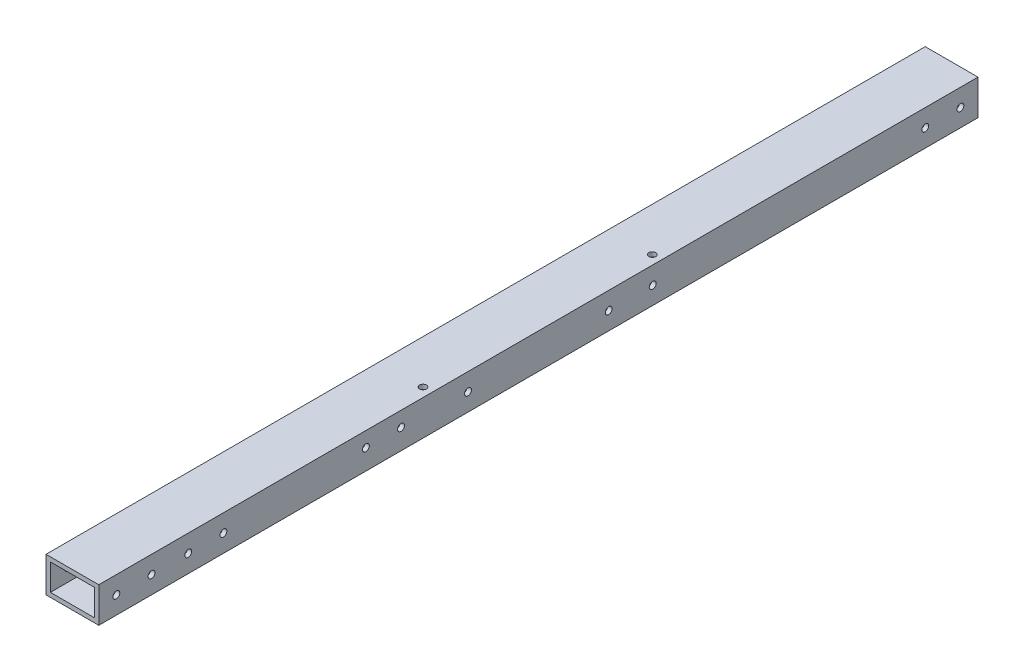
SolidWorks part; units mm, degrees
material "1060 Alloy"
ref_plane "Front Plane" through (0, 0, 0) normal (0, 0, 1) x (1, 0, 0)
ref_plane "Top Plane" through (0, 0, 0) normal (0, 1, 0) x (1, 0, 0)
ref_plane "Right Plane" through (0, 0, 0) normal (1, 0, 0) x (0, 0, -1)
sketch "Sketch1" plane through (0, 0, 0) normal (0, 0, 1) x (1, 0, 0)
  line L0 (-15.875, 9.525) -> (15.875, 9.525)
  line L2 (-19.05, 12.7) -> (19.05, 12.7)
  line L3 (-19.05, 12.7) -> (-19.05, -12.7)
  line L4 (-19.05, -12.7) -> (19.05, -12.7)
  line L5 (19.05, 12.7) -> (19.05, -12.7)
  line L10 (15.875, 9.525) -> (15.875, -9.525)
  line L11 (-15.875, -9.525) -> (15.875, -9.525)
  line L12 (-15.875, 9.525) -> (-15.875, -9.525)
  point P12 (0, 12.7)
  point P14 (19.05, 0)
  dimension "Wall Thickness" = 3.175
  dimension "Outside Width" = 38.1
  dimension "Outside Height" = 25.4
  dimension "Inside Height" = 19.05
  dimension "Inside Width" = 31.75
sketch "Sketch2" plane through (0, 0, 0) normal (1, 0, 0) x (0, 0, -1)
  line L0 (317.5, 0) -> (-317.5, 0)
  point P4 (0, 0)
  point P7 (-317.5, 0)
  point P10 (317.5, 0)
  dimension "Length" = 635
sketch "Sketch3" plane through (0, 0, 0) normal (0, 0, 1) x (1, 0, 0)
  line L21 (19.05, 12.7) -> (-19.05, 12.7)
  line L22 (19.05, -12.7) -> (19.05, 12.7)
  line L23 (-19.05, -12.7) -> (19.05, -12.7)
  line L24 (-19.05, 12.7) -> (-19.05, -12.7)
  line L25 (19.05, 12.7) -> (-19.05, 12.7)
  line L26 (19.05, -12.7) -> (19.05, 12.7)
  line L27 (-19.05, -12.7) -> (19.05, -12.7)
  line L28 (-19.05, 12.7) -> (-19.05, -12.7)
  line L29 (15.875, 9.525) -> (-15.875, 9.525)
  line L30 (15.875, -9.525) -> (15.875, 9.525)
  line L31 (-15.875, -9.525) -> (15.875, -9.525)
  line L32 (-15.875, 9.525) -> (-15.875, -9.525)
  line L33 (15.875, 9.525) -> (-15.875, 9.525)
  line L34 (15.875, -9.525) -> (15.875, 9.525)
  line L35 (-15.875, -9.525) -> (15.875, -9.525)
  line L36 (-15.875, 9.525) -> (-15.875, -9.525)
  dimension "D1" = 0
  dimension "D2" = 0
extrude "Boss-Extrude1" add sketch "Sketch3" along normal up to vertex (317.5 mm away) and the other way up to vertex (317.5 mm away) up to point (0, 0, 317.5) other way up to point (0, 0, -317.5)
sketch "Drawing Reference" plane through (0, 0, 0) normal (1, 0, 0) x (0, 0, -1)
  line L0 (-317.5, 0) -> (317.5, 0) construction
  line L1 (0, -12.7) -> (0, 12.7) construction
  line L2 (-317.5, -12.7) -> (317.5, -12.7) construction
  line L5 (-317.5, 12.7) -> (317.5, 12.7) construction
  point P7 (-290.068, 0)
  point P8 (290.068, 0)
  dimension "D1" = 27.432
sketch "Sketch4" plane through (-19.05, 0, 0) normal (-1, 0, 0) x (0, 0, 1)
  line L0 (-317.5, 0) -> (-304.8, 0)
  line L1 (-317.5, 12.7) -> (-317.5, -12.7) construction
  line L2 (-304.8, 0) -> (-279.4, 0)
  line L3 (317.5, 12.7) -> (317.5, -12.7) construction
  line L4 (317.5, 0) -> (304.8, 0)
  line L5 (304.8, 0) -> (279.4, 0)
  line L6 (0, 0) -> (50.8, 0) construction
  line L7 (0, 0) -> (-50.8, 0) construction
  point P11 (-304.8, 0)
  point P13 (-279.4, 0)
  point P14 (304.8, 0)
  point P15 (279.4, 0)
hole_wizard "#10 Clearance Hole2" positions "Sketch11" profile "Sketch12" hole size "#10" standard "ANSI Inch" end condition through all
sketch "Sketch11" plane through (-19.05, 0, 0) normal (-1, 0, 0) x (0, 0, 1)
  point P0 (-304.8, 0)
  point P3 (-279.4, 0)
  point P6 (279.4, 0)
  point P9 (304.8, 0)
sketch "Sketch12" plane through (-19.05, 0, -304.8) normal (0, 1, 0) x (0, 0, 1)
  line L0 (0, 0) -> (0, 38.1)
  line L1 (0, 38.1) -> (2.4892, 38.1)
  line L2 (2.4892, 38.1) -> (2.4892, 0)
  line L5 (2.4892, 0) -> (0, 0)
  line L11 (0, -6.35) -> (0, 107.95) construction
  dimension "Thru Hole Dia." = 4.9784
  dimension "Thru Hole Depth" = 38.1
hole_wizard "#10 Clearance Hole4" positions "Sketch14" profile "Sketch16" hole size "#10" standard "ANSI Inch" end condition through all
sketch "Sketch14" plane through (19.05, 0, 0) normal (1, 0, 0) x (0, 0, -1)
  point P33 (-252.857, 0)
  point P36 (-227.457, 0)
  point P42 (-124.587, 1.9434)
  point P45 (-99.187, 1.9434)
sketch "Sketch16" plane through (19.05, 0, 252.857) normal (0, 1, 0) x (0, 0, -1)
  line L0 (0, 0) -> (0, 38.1)
  line L1 (0, 38.1) -> (2.4892, 38.1)
  line L2 (2.4892, 38.1) -> (2.4892, 0)
  line L5 (2.4892, 0) -> (0, 0)
  line L11 (0, -6.35) -> (0, 107.95) construction
  dimension "Thru Hole Dia." = 4.9784
  dimension "Thru Hole Depth" = 38.1
hole_wizard "#10 Clearance Hole3" positions "Sketch20" profile "Sketch21" hole size "#10" standard "ANSI Inch" end condition through all
sketch "Sketch20" plane through (-19.05, 0, 0) normal (-1, 0, 0) x (0, 0, 1)
  point P0 (-50.8, 0)
  point P3 (50.8, 0)
sketch "Sketch21" plane through (-19.05, 0, -50.8) normal (0, 1, 0) x (0, 0, 1)
  line L0 (0, 0) -> (0, 38.1)
  line L1 (0, 38.1) -> (2.4892, 38.1)
  line L2 (2.4892, 38.1) -> (2.4892, 0)
  line L5 (2.4892, 0) -> (0, 0)
  line L11 (0, -6.35) -> (0, 107.95) construction
  dimension "Thru Hole Dia." = 4.9784
  dimension "Thru Hole Depth" = 38.1
sketch "Sketch22" plane through (19.05, 0, 0) normal (1, 0, 0) x (0, 0, -1)
  line L0 (50.8, 0) -> (82.55, 0) construction
hole_wizard "#10 Clearance Hole5" positions "Sketch23" profile "Sketch24" hole size "#10" standard "ANSI Inch" end condition through all
sketch "Sketch23" plane through (19.05, 0, 0) normal (1, 0, 0) x (0, 0, -1)
  point P0 (82.55, 0)
sketch "Sketch24" plane through (19.05, 0, -82.55) normal (0, 1, 0) x (0, 0, -1)
  line L0 (0, 0) -> (0, 38.1)
  line L1 (0, 38.1) -> (2.4892, 38.1)
  line L2 (2.4892, 38.1) -> (2.4892, 0)
  line L5 (2.4892, 0) -> (0, 0)
  line L11 (0, -6.35) -> (0, 107.95) construction
  dimension "Thru Hole Dia." = 4.9784
  dimension "Thru Hole Depth" = 38.1
sketch "Sketch25" plane through (0, -12.7, 0) normal (0, -1, 0) x (1, 0, 0)
  line L0 (12.4668, -88.9) -> (12.4668, 76.7543) construction
  point P2 (12.4668, -88.9)
  point P3 (12.4668, 76.7543)
hole_wizard "#10 Clearance Hole6" positions "Sketch26" profile "Sketch27" hole size "#10" standard "ANSI Inch" end condition through all
sketch "Sketch26" plane through (0, -12.7, 0) normal (0, -1, 0) x (-1, 0, 0)
  point P0 (-12.4668, -76.7543)
  point P3 (-12.4668, 88.9)
sketch "Sketch27" plane through (12.4668, -12.7, 76.7543) normal (1, 0, 0) x (0, 0, -1)
  line L0 (0, 0) -> (0, 25.4)
  line L1 (0, 25.4) -> (2.4892, 25.4)
  line L2 (2.4892, 25.4) -> (2.4892, 0)
  line L5 (2.4892, 0) -> (0, 0)
  line L11 (0, -6.35) -> (0, 107.95) construction
  dimension "Thru Hole Dia." = 4.9784
  dimension "Thru Hole Depth" = 25.4
equation "\"D1@Drawing Reference\"=\"Outside Width@Sketch1\" * 0.72"
